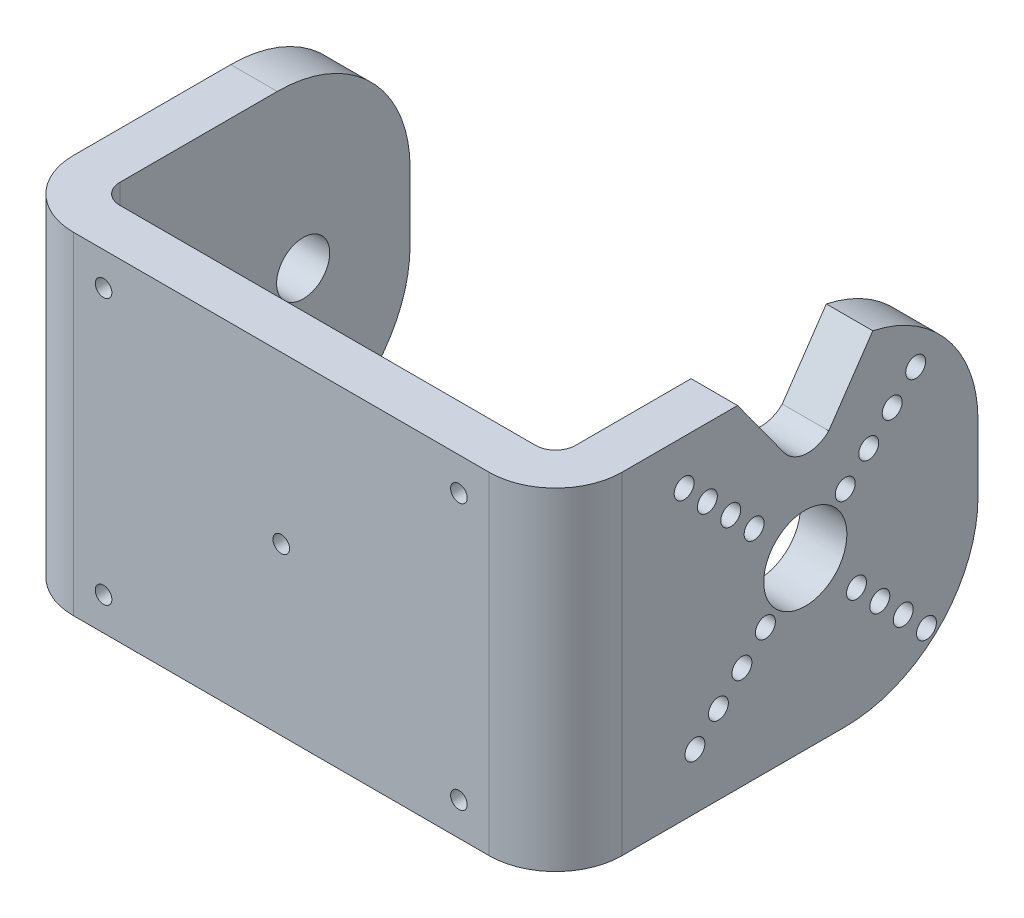
SolidWorks part; units mm, degrees
ref_plane "Front Plane" through (0, 0, 0) normal (0, 0, 1) x (1, 0, 0)
ref_plane "Top Plane" through (0, 0, 0) normal (0, 1, 0) x (1, 0, 0)
ref_plane "Right Plane" through (0, 0, 0) normal (1, 0, 0) x (0, 0, -1)
sketch "Sketch1" plane through (0, 0, 0) normal (0, 1, 0) x (1, 0, 0)
  line L0 (-56.3757, 54.198) -> (-56.3757, 10.498)
  line L1 (26.2243, 64.098) -> (26.2243, 10.498)
  line L2 (-46.3757, 0.498) -> (16.2243, 0.498)
  line L3 (-49.3757, 54.198) -> (-49.3757, 10.498)
  line L4 (-46.3757, 7.498) -> (16.2243, 7.498)
  line L5 (19.2243, 64.098) -> (19.2243, 10.498)
  line L6 (19.2243, 64.098) -> (26.2243, 64.098)
  line L7 (-49.3757, 54.198) -> (-56.3757, 54.198)
  arc A0 (-56.3757, 10.498) -> (-46.3757, 0.498) centre (-46.3757, 10.498) ccw
  arc A1 (16.2243, 0.498) -> (26.2243, 10.498) centre (16.2243, 10.498) ccw
  arc A2 (-49.3757, 10.498) -> (-46.3757, 7.498) centre (-46.3757, 10.498) ccw
  arc A3 (16.2243, 7.498) -> (19.2243, 10.498) centre (16.2243, 10.498) ccw
  dimension "D1" = 10
  dimension "D3" = 10
  dimension "D2" = 82.6
  dimension "D4" = 46.7
  dimension "D6" = 63.6
  dimension "D5" = 7
extrude "Boss-Extrude1" add sketch "Sketch1" along normal blind 50
fillet "Fillet2" radius 20 4 edges at (-52.8757, 50, -54.198) (-52.8757, 0, -54.198) (22.7243, 0, -64.098) (22.7243, 50, -64.098)
sketch "Sketch6" plane through (26.2243, 0, 0) normal (1, 0, 0) x (0, 0, -1)
  line L0 (64.098, 30) -> (64.098, 20) construction
  line L1 (85.3454, 25) -> (-15.2119, 25) construction
  circle A0 centre (38.098, 25) radius 4
  point P5 (64.098, 25)
  line B0 (19.0389, 5.9409) -> (56.3034, 43.2054) construction
  line B1 (-1276.2531, -1372.4722) -> (-849.632, -945.8511) construction
  line B2 (19.1731, 5.8923) -> (56.5233, 42.9855) construction
  line B3 (-122.2936, 133.0666) -> (-69.2606, 186.0996) construction
  line B4 (33.6703, 29.4276) -> (42.5256, 20.5724) construction
  line B5 (19.8546, 43.2434) -> (59.051, 4.047) construction
  circle B6 centre (19.8546, 43.2434) radius 1.5
  circle B7 centre (23.3548, 39.7432) radius 1.5
  circle B8 centre (26.8762, 36.2218) radius 1.5
  circle B9 centre (30.3905, 32.7075) radius 1.5
  circle B10 centre (32.0876, 18.9896) radius 1.5
  circle B11 centre (28.552, 15.4541) radius 1.5
  circle B12 centre (25.0165, 11.9185) radius 1.5
  circle B13 centre (21.481, 8.383) radius 1.5
  circle B14 centre (38.098, 25) radius 6.2616
  circle B15 centre (-8.1988, -9.2742) radius 3.25 construction
  circle B16 centre (3.822, -21.295) radius 3.25 construction
  circle B17 centre (44.8342, 43.7588) radius 3.25 construction
  circle B18 centre (56.855, 31.738) radius 3.25 construction
  circle B19 centre (44.1084, 31.0104) radius 1.5
  circle B20 centre (47.6439, 34.5459) radius 1.5
  circle B21 centre (51.1795, 38.0815) radius 1.5
  circle B22 centre (54.715, 41.617) radius 1.5
  circle B23 centre (56.3413, 6.7566) radius 1.5
  circle B24 centre (52.8412, 10.2568) radius 1.5
  circle B25 centre (49.3198, 13.7782) radius 1.5
  circle B26 centre (45.8054, 17.2925) radius 1.5
  dimension "D2" = 8
  dimension "D1" = 26
sketch_block_instance "Block-Sketch2-2"
sketch_block "Block-Sketch2" parameters "D2"=3, "D3"=3, "D4"=3, "D5"=3, "D6"=3, "D7"=3, "D8"=3, "D9"=3, "D10"=6.5, "D11"=6.5, "D12"=6.5, "D1"=52.7, "D13"=75, "D14"=17, "D15"=75, "D16"=8.5, "D17"=13.5, "D18"=18.5, "D19"=23.5, "D20"=10.9, "D21"=15.87, "D22"=20.85, "D23"=25.8
extrude "Cut-Extrude2" cut sketch "Sketch6" against normal blind 28.4 contours A0 L1 | L1 A0 | L1 B14 A0 | B14 L1 A0 | B9 | B8 | B7 | B6 | B19 | B20 | B21 | B22 | B26 | B25 | B24 | B23 | B10 | B11 | B12 | B13 region at (26.2243, 18.8784, -38.098) region at (26.2243, 25.14, -43.2288) region at (26.2243, 23.3023, -38.098) region at (26.2243, 26.6977, -38.098) region at (26.2243, 43.2434, -19.8546) region at (26.2243, 39.7432, -23.3548) region at (26.2243, 36.2218, -26.8762) region at (26.2243, 32.7075, -30.3905) region at (26.2243, 18.9896, -32.0876) region at (26.2243, 15.4541, -28.552) region at (26.2243, 11.9185, -25.0165) region at (26.2243, 8.383, -21.481) region at (26.2243, 31.0104, -44.1084) region at (26.2243, 34.5459, -47.6439) region at (26.2243, 38.0815, -51.1795) region at (26.2243, 41.617, -54.715) region at (26.2243, 6.7566, -56.3413) region at (26.2243, 10.2568, -52.8412) region at (26.2243, 13.7782, -49.3198) region at (26.2243, 17.2925, -45.8054)
extrude "Cut-Extrude3" cut sketch "Sketch6<3>" against normal blind 136.4 contours L1 A0 | A0 L1 region at (26.2243, 23.3023, -38.098) region at (26.2243, 26.6977, -38.098)
sketch "Sketch6<3>" plane through (26.2243, 0, 0) normal (1, 0, 0) x (0, 0, -1) same geometry as "Sketch6"
sketch "Sketch7" plane through (26.2243, 0, 0) normal (1, 0, 0) x (0, 0, -1)
  line L0 (27.9014, 50) -> (34.8899, 40.3636)
  line L1 (10.498, 50) -> (44.098, 50) construction
  line L2 (41.6295, 39.8302) -> (48.2623, 49.5617)
  arc A0 (34.8899, 40.3636) -> (41.6295, 39.8302) centre (38.4873, 42.9724) ccw
  arc A1 (64.098, 30) -> (44.098, 50) centre (44.098, 30) ccw construction
  arc M16 (64.098, 30) -> (44.098, 50) centre (44.098, 30) ccw
  line M17 (44.098, 50) -> (10.498, 50)
extrude "Cut-Extrude4" cut sketch "Sketch7" against normal blind 26.4 and the other way through all contours L0 A0 L2 M16 M17 region at (26.2243, 45.5364, -38.2869)
sketch "Sketch8" plane through (0, 0, -0.498) normal (0, 0, 1) x (1, 0, 0)
  line L0 (-46.3757, 25) -> (16.2243, 25) construction
  line L1 (-46.3757, 50) -> (-46.3757, 0) construction
  line L2 (16.2243, 50) -> (16.2243, 0) construction
  line L3 (-15.0757, 6.2475) -> (-15.0757, 55.8206) construction
  circle A0 centre (-41.8257, 45) radius 1.25
  circle A1 centre (11.6743, 45) radius 1.25
  circle A2 centre (-15.0757, 25) radius 1.25
  circle A3 centre (-41.8257, 5) radius 1.25
  circle A4 centre (11.6743, 5) radius 1.25
  point P10 (0, 0)
  point P15 (-15.0757, 25)
  dimension "D1" = 2.5
  dimension "D2" = 2.5
  dimension "D3" = 2.5
  dimension "D4" = 2.5
  dimension "D5" = 2.5
  dimension "D6" = 40
  dimension "D7" = 53.5
extrude "Cut-Extrude5" cut sketch "Sketch8" against normal blind 5
equation "\"D3@Sketch1\"=\"D1@Sketch1\""
equation "\"D2@Sketch8\"=\"D1@Sketch8\""
equation "\"D3@Sketch8\"=\"D2@Sketch8\""
equation "\"D4@Sketch8\"=\"D3@Sketch8\""
equation "\"D5@Sketch8\"=\"D3@Sketch8\""
